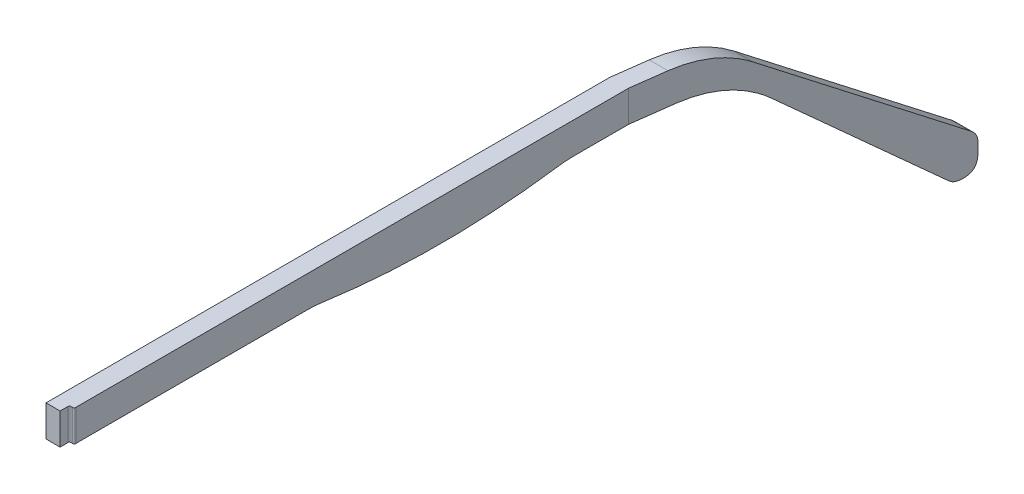
SolidWorks part; units mm, degrees
ref_plane "Front Plane" through (0, 0, 0) normal (0, 0, 1) x (1, 0, 0)
ref_plane "Top Plane" through (0, 0, 0) normal (0, 1, 0) x (1, 0, 0)
ref_plane "Right Plane" through (0, 0, 0) normal (1, 0, 0) x (0, 0, -1)
sketch "Sketch2" plane through (0, 0, 0) normal (0, 1, 0) x (1, 0, 0)
  line L0 (0, 0) -> (0, 90)
  line L1 (0, 90) -> (0, 140) construction
  line L3 (-3, 0) -> (0, 0)
  line L5 (0, 90) -> (-6.4875, 139.2772)
  line L6 (-6.4875, 139.2772) -> (-9.4875, 139.2772)
  line L7 (-9.4875, 139.2772) -> (-3, 90)
  line L8 (-3, 90) -> (-3, 0)
  dimension "D1" = 90
  dimension "D2" = 50
  dimension "D3" = 3
  dimension "D4" = 7.5
  dimension "D5" = 6.4875
extrude "Boss-Extrude1" add sketch "Sketch2" against normal blind 33
sketch "Sketch3" plane through (0, 0, 0) normal (1, 0, 0) x (0, 0, -1)
  line L0 (0, 0) -> (0, -5)
  line L1 (0, -33) -> (0, 0) construction
  line L2 (0, -5) -> (38.5524, -5)
  line L3 (40, -6.5) -> (80, -6.5) construction
  line L4 (81.4476, -5) -> (90, -5)
  line L5 (90, -33) -> (90, 0) construction
  line L6 (90, -5) -> (96.7662, -5)
  line L7 (110.0726, -10.0688) -> (135.8038, -33)
  line L8 (90, -33) -> (139.2772, -33) construction
  line L9 (0, 0) -> (40, 0)
  line L10 (0, 0) -> (90, 0) construction
  line L11 (40, 0) -> (80, 0)
  line L12 (80, 0) -> (90, 0)
  line L13 (90, 0) -> (95.5526, 0)
  line L14 (90, 0) -> (139.2772, 0) construction
  line L15 (107.507, -3.9659) -> (139.2772, -27.6526)
  line L16 (139.2772, -33) -> (139.2772, 0) construction
  line L17 (104.3849, -5) -> (108.894, -5) construction
  line L18 (108.894, -5) -> (106.898, -7.2397) construction
  line L19 (90, -33) -> (139.2772, -33)
  line L20 (139.2772, -33) -> (139.2772, 0)
  line L21 (90, 0) -> (139.2772, 0)
  line L25 (90, 0) -> (0, 0)
  line L26 (0, 0) -> (0, -33)
  line L27 (0, -33) -> (90, -33)
  line L28 (90, -33) -> (90, 0)
  line L29 (90, 0) -> (0, 0)
  line L30 (0, 0) -> (0, -33)
  line L31 (0, -33) -> (90, -33)
  line L32 (90, -33) -> (90, 0) construction
  arc A0 (41.3363, -5.1947) -> (78.6637, -5.1947) centre (60, 127.5833) ccw
  arc A1 (95.5526, 0) -> (107.507, -3.9659) centre (95.5526, -20) cw
  arc A2 (96.7662, -5) -> (110.0726, -10.0688) centre (96.7662, -25) cw
  arc A3 (81.4476, -5) -> (78.6637, -5.1947) centre (81.4476, -25) ccw
  arc A4 (38.5524, -5) -> (41.3363, -5.1947) centre (38.5524, -25) cw
  point P32 (102.1877, 0)
  point P38 (80, -5)
  point P41 (40, -5)
  line M11 (0, 0) -> (0, -33)
  line M12 (0, -33) -> (90, -33)
  line M13 (90, -33) -> (90, 0)
  dimension "D7" = 20
  dimension "D1" = 5
  dimension "D2" = 40
  dimension "D3" = 6.5
  dimension "D4" = 10
  dimension "D5" = 5
  dimension "D6" = 3
  dimension "D8" = 0
extrude "Cut-Extrude1" cut sketch "Sketch3" against normal through all contours A4 L2 L4 A3 A0 M11 M12 M13 | A2 L6 L19 L7 M13 | L21 A1 L15 L20 region at (0, -19.2169, -44.7572) region at (0, -21.5611, -106.4336) region at (0, -9.1433, -126.6932)
fillet "Fillet2" radius 3 3 edges at (-7.5302, -33, -135.8038) (-7.9875, -33, -139.2772) (-7.9875, -27.6526, -139.2772) curvature continuous yes
mirror "Mirror1" about plane through (-3, -33, -90) normal (-1, 0, 0) of bodies 103
delete or keep bodies "Body-Delete/Keep 1" type delete bodies bodies 103
sketch "Sketch4" plane through (0, 0, 0) normal (0, 1, 0) x (1, 0, 0)
  line L1 (-3, 0) -> (-3.75, 0)
  line L2 (-3, 0) -> (-3, 1.5)
  line L3 (-3, 1.5) -> (-3.75, 1.5)
  line L4 (-3.75, 0) -> (-3.75, 1.5)
  dimension "D1" = 0.75
  dimension "D2" = 1.5
extrude "Cut-Extrude2" cut sketch "Sketch4" against normal through all both and the other way through all
fillet "Fillet3" radius 0.25 2 edges at (-3.75, -2.5, -1.5) (-3, -2.5, -1.5) curvature continuous yes
